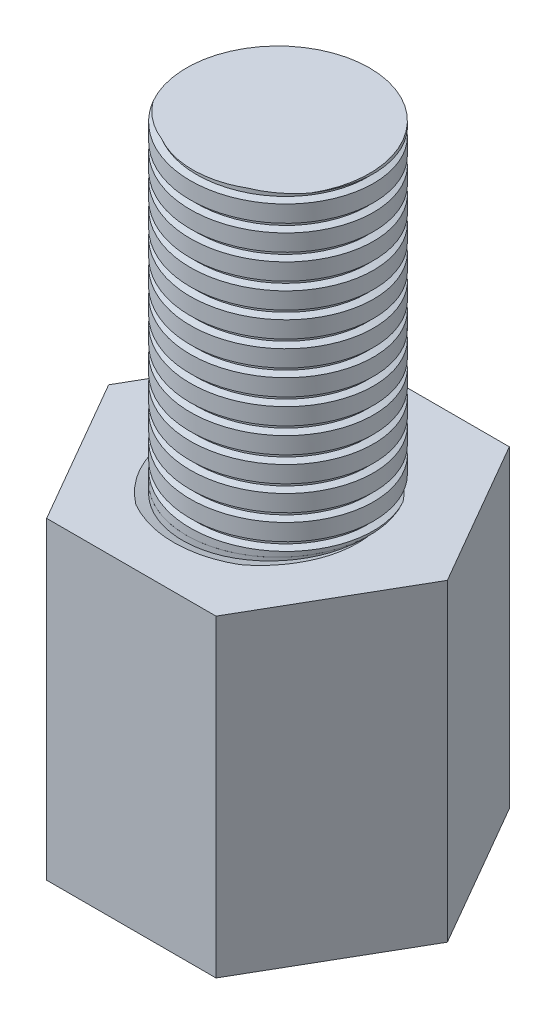
SolidWorks part; units mm, degrees
note: The reader was unsure of these and kept them because the rebuilt part matched: shared geometry of "草图1<3>".
ref_plane "前视基准面" through (0, 0, 0) normal (0, 0, 1) x (1, 0, 0)
ref_plane "上视基准面" through (0, 0, 0) normal (0, 1, 0) x (1, 0, 0)
ref_plane "右视基准面" through (0, 0, 0) normal (1, 0, 0) x (0, 0, -1)
sketch "草图1" plane through (0, 0, 0) normal (0, 1, 0) x (1, 0, 0)
  line L0 (0, 0) -> (0, 4.5761) construction
  line L1 (1.351, -2.34) -> (2.702, 0)
  line L2 (2.702, 0) -> (1.351, 2.34)
  line L3 (1.351, 2.34) -> (-1.351, 2.34)
  line L4 (-1.351, 2.34) -> (-2.702, 0)
  line L5 (-2.702, 0) -> (-1.351, -2.34)
  line L6 (-1.351, -2.34) -> (1.351, -2.34)
  line L7 (0, 4.5761) -> (0, -3.6794) construction
  circle A0 centre (0, 0) radius 2.34 construction
  circle A1 centre (0, 0) radius 1.46
  dimension "D1" = 4.68
  dimension "D2" = 2.92
extrude "凸台-拉伸1" add sketch "草图1" along normal blind 5 contours A1 | L5 L6 L1 L2 L3 L4 A1
extrude "切除-拉伸1" cut sketch "草图1<3>" along normal blind 2.5 contours A1
sketch "草图1<3>" plane through (0, 0, 0) normal (0, 1, 0) x (1, 0, 0) same geometry as "草图1"
sketch "草图2" plane through (0, 5, 0) normal (0, 1, 0) x (1, 0, 0)
  circle A0 centre (0, 0) radius 1.46
  dimension "D1" = 2.92
extrude "凸台-拉伸2" add sketch "草图2" along normal blind 5 separate body
ref_plane "基准面1" through (0, 0, 0) normal (0, 0, -1) x (-1, 0, 0)
sketch "草图4" plane through (0, 0, 0) normal (0, 0, -1) x (-1, 0, 0)
  line L0 (0, 0) -> (0, 28.5702) construction
  line L1 (-1.56, 5) -> (-1.56, 5.2)
  line L2 (-1.56, 5.2) -> (-1.36, 5.1333)
  line L3 (-1.36, 5.0667) -> (-1.56, 5)
  line L4 (-1.26, 5.1) -> (-2.0659, 5.1) construction
  line L5 (-2.0659, 5.1) -> (-0.8933, 5.1) construction
  line L7 (-1.46, 10) -> (-1.46, 5) construction
  line L8 (-1.36, 5.1333) -> (-1.36, 5.0667)
  line L9 (-1.46, 5) -> (1.46, 5) construction
  point P14 (0, 0)
  point P15 (0, 0)
  dimension "D1" = 0.1
  dimension "D2" = 0.1
  dimension "D3" = 0.1
  dimension "D4" = 0.3
  dimension "D5" = 0.2
  dimension "D6" = 0.1
  dimension "D7" = 0.0667
  dimension "D8" = 0.0667
ref_plane "基准面2" through (0, 5.1, 0) normal (0, 1, 0) x (1, 0, 0)
sketch "草图5" plane through (0, 5.1, 0) normal (0, 1, 0) x (1, 0, 0)
  circle A0 centre (0, 0) radius 1.46
  dimension "D1" = 2.92
curve "螺旋线/涡状线1" pitch 0.4 height 7.5 turns 18.75
sweep "切除-扫描1" cut profiles "草图4" path "螺旋线/涡状线1"
sketch "草图6" plane through (0, 0, 0) normal (0, -1, 0) x (1, 0, 0)
  circle A0 centre (0, 0) radius 1.46
curve "螺旋线/涡状线2" pitch 0.4 height 9.5 turns 23.75
sketch "草图7" plane through (0, 0, 0) normal (0, 0, -1) x (-1, 0, 0)
  line L0 (1.46, 0.2) -> (1.66, 0.1333)
  line L1 (1.66, 0.0667) -> (1.46, 0)
  line L2 (1.46, 0.2) -> (1.46, 0)
  line L3 (1.66, 0.1333) -> (1.66, 0.0667)
  line L8 (1.351, 0) -> (-1.351, 0) construction
  dimension "D1" = 0.2
  dimension "D3" = 1.46
  dimension "D4" = 0.2
sweep "切除-扫描2" cut profiles "草图7" path "螺旋线/涡状线2"
equation "\"chang\"= 20mm"
equation "\"r\"= 2.92mm"
equation "\"luowengao\"= 6.5mm"
equation "\"rr\"= 4.68mm"
equation "\"D1@草图1\"=\"rr\""
equation "\"D2@草图1\"=\"r\""
equation "\"D1@凸台-拉伸1\"=\"chang\""
equation "\"D1@切除-拉伸1\"=\"luowengao\"+5mm"
equation "\"D1@草图2\"=\"r\""
equation "\"D1@凸台-拉伸2\"=\"luowengao\""
